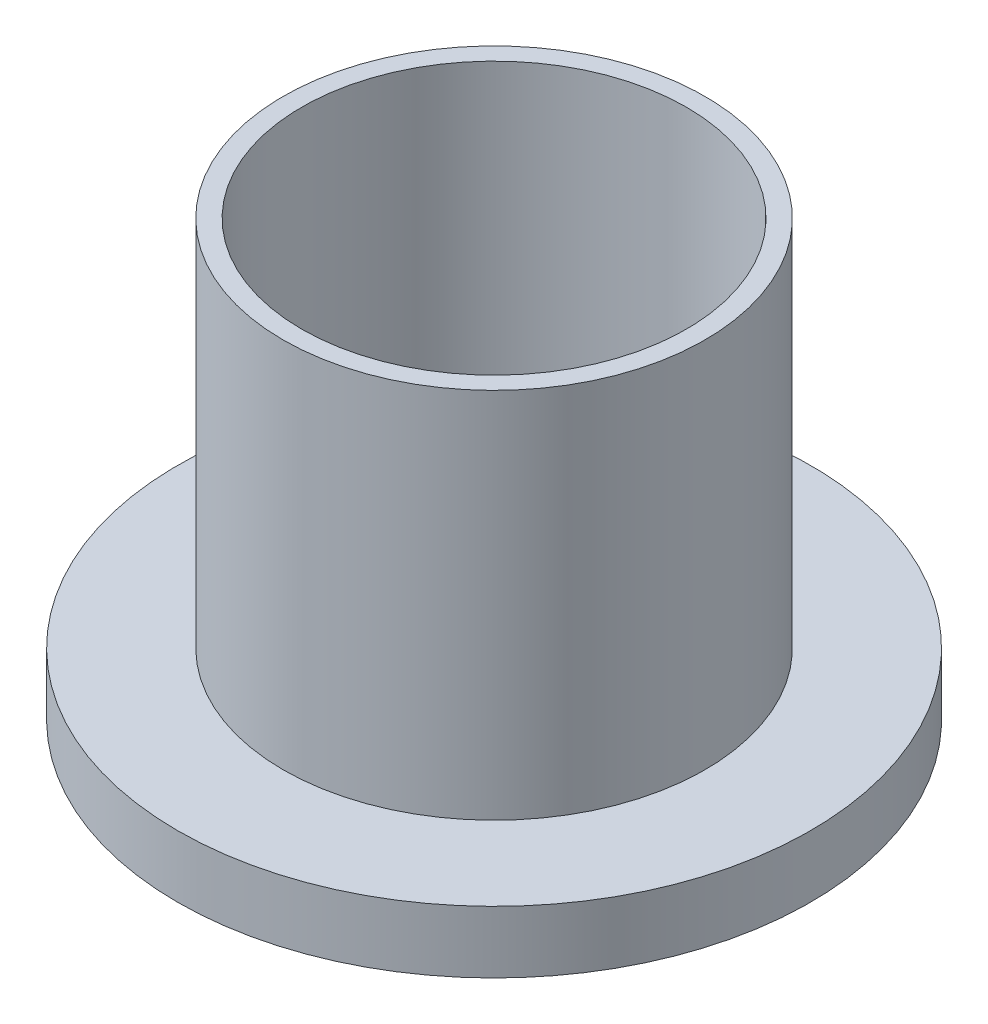
SolidWorks part; units mm, degrees
ref_plane "Plan de face" through (0, 0, 0) normal (0, 0, 1) x (1, 0, 0)
ref_plane "Plan de dessus" through (0, 0, 0) normal (0, 1, 0) x (1, 0, 0)
ref_plane "Plan de droite" through (0, 0, 0) normal (1, 0, 0) x (0, 0, -1)
sketch "Esquisse1" plane through (0, 0, 0) normal (0, 1, 0) x (1, 0, 0)
  circle A0 centre (0, 0) radius 5.1
  circle A2 centre (0, 0) radius 3.1
  dimension "D1" = 10.2
  dimension "D2" = 6.2
extrude "Boss.-Extru.1" add sketch "Esquisse1" along normal blind 1
sketch "Esquisse2" plane through (0, 1, 0) normal (0, 1, 0) x (1, 0, 0)
  circle A0 centre (0, 0) radius 3.4
  circle A1 centre (0, 0) radius 3.1
  circle A2 centre (0, 0) radius 3.1 construction
  dimension "D1" = 6.8
extrude "Boss.-Extru.2" add sketch "Esquisse2" along normal blind 6
ref_axis "Axe1" through (0, 7, 0) along (0, -1, 0)
